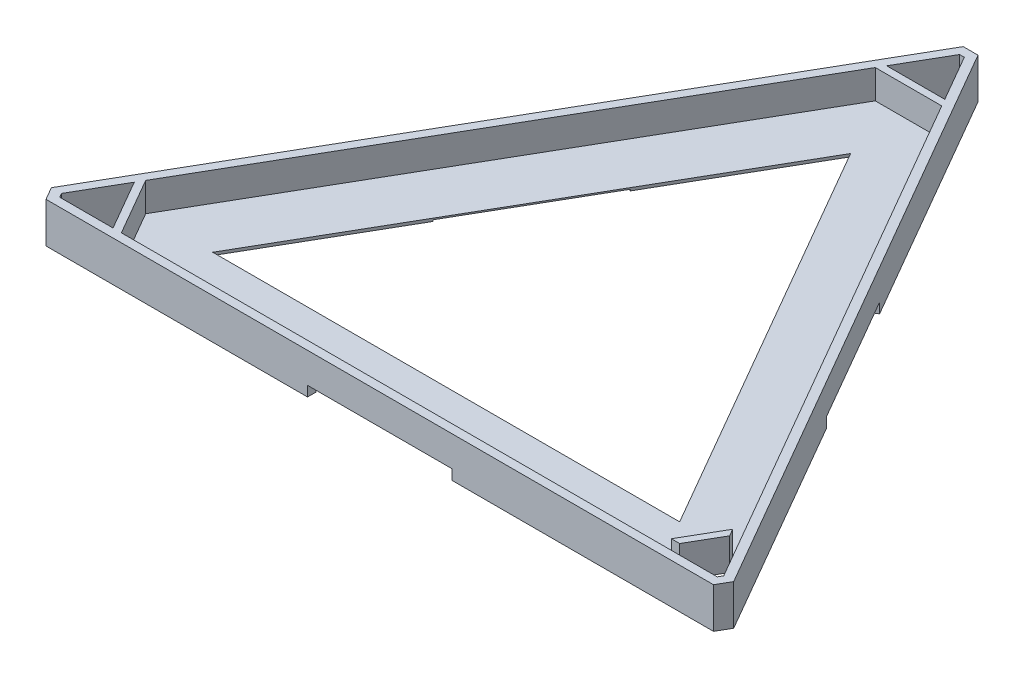
SolidWorks part; units mm, degrees
ref_plane "Front Plane" through (0, 0, 0) normal (0, 0, 1) x (1, 0, 0)
ref_plane "Top Plane" through (0, 0, 0) normal (0, 1, 0) x (1, 0, 0)
ref_plane "Right Plane" through (0, 0, 0) normal (1, 0, 0) x (0, 0, -1)
sketch "Sketch1" plane through (0, 0, 0) normal (0, 1, 0) x (1, 0, 0)
  line L0 (351.2729, 67.6655) -> (468.273, -134.9846)
  line L1 (347.2728, 67.6655) -> (347.2728, 65.1655) construction
  line L2 (409.773, -33.6595) -> (407.6079, -34.9095) construction
  line L3 (468.273, -134.9846) -> (464.2732, -141.9124)
  line L4 (230.2733, -141.9124) -> (464.2732, -141.9124)
  line L5 (230.2733, -141.9124) -> (226.2727, -134.9842)
  line L6 (226.2727, -134.9842) -> (343.2728, 67.6655)
  line L7 (353.4142, 63.9567) -> (351.2491, 62.7067) construction
  line L8 (347.2733, -141.9124) -> (347.2733, -139.4124) construction
  line L9 (231.7167, -139.4124) -> (462.8299, -139.4124)
  line L10 (284.7727, -33.6594) -> (286.9378, -34.9094) construction
  line L11 (344.7161, 65.1655) -> (349.8295, 65.1655)
  line L12 (465.3862, -134.9846) -> (349.8295, 65.1655)
  line L13 (466.2731, -138.4485) -> (464.1081, -137.1985) construction
  line L14 (462.8299, -139.4124) -> (465.3862, -134.9846)
  line L15 (229.1594, -134.9842) -> (344.7161, 65.1655)
  line L16 (229.1594, -134.9842) -> (231.7167, -139.4124)
  line L17 (286.9378, -34.9094) -> (287.3708, -35.1594) construction
  line L18 (230.438, -137.1983) -> (230.871, -136.9483) construction
  line L19 (232.0053, -138.9123) -> (229.7368, -134.9842)
  line L20 (343.2728, 67.6655) -> (351.2729, 67.6655)
  line L21 (345.0048, 64.6655) -> (229.7368, -134.9842)
  line L22 (349.5409, 64.6655) -> (345.0048, 64.6655)
  line L23 (249.0568, -126.4468) -> (246.8918, -127.697) construction
  line L24 (407.6079, -34.9095) -> (407.1749, -35.1595) construction
  line L26 (233.4463, -136.4089) -> (251.9226, -136.4093)
  line L27 (464.8089, -134.9846) -> (462.5412, -138.9123)
  line L28 (462.5412, -138.9123) -> (232.0053, -138.9123)
  line L29 (251.9226, -136.4093) -> (241.8609, -118.9847)
  line L30 (241.8609, -118.9847) -> (232.6236, -134.9842)
  line L31 (232.6236, -134.9842) -> (233.4463, -136.4089)
  line L33 (287.3708, -35.1594) -> (289.5359, -36.4094) construction
  line L34 (254.8093, -136.4089) -> (243.3042, -116.4848)
  line L35 (335.7675, 43.666) -> (243.3042, -116.4848)
  line L36 (358.7782, 43.666) -> (335.7675, 43.666)
  line L38 (289.5359, -36.4094) -> (306.8564, -46.4094) construction
  line L41 (461.939, -134.9846) -> (461.1164, -136.4093)
  line L42 (347.2688, -136.4172) -> (347.2688, -116.4172) construction
  line L43 (442.6021, -136.4093) -> (452.6999, -118.9847)
  line L44 (245.2636, -119.878) -> (249.0568, -126.4468) construction
  line L45 (452.6999, -118.9847) -> (461.939, -134.9846)
  line L48 (461.1164, -136.4093) -> (442.6021, -136.4093)
  line L49 (405.0134, -36.4027) -> (387.6936, -46.404) construction
  line L50 (306.8564, -46.4094) -> (466.2731, -138.4485) construction
  line L51 (357.3348, 46.166) -> (337.2109, 46.166)
  line L52 (337.2109, 46.166) -> (346.4484, 62.1659)
  line L53 (346.4484, 62.1659) -> (348.0966, 62.164)
  line L54 (348.0966, 62.164) -> (357.3348, 46.166)
  line L55 (228.273, -138.4483) -> (387.6936, -46.404) construction
  line L56 (347.2688, -116.4172) -> (347.2728, 43.666) construction
  line L57 (266.4391, -116.428) -> (428.1137, -116.4172)
  line L58 (347.2736, 23.6092) -> (428.1137, -116.4172)
  line L59 (266.4391, -116.428) -> (347.2736, 23.6092)
  line L60 (439.7283, -136.4254) -> (439.7283, -132.9254) construction
  line L61 (451.2487, -116.4715) -> (448.6507, -117.9717) construction
  line L62 (452.6999, -118.9847) -> (358.7782, 43.666)
  line L63 (442.6021, -136.4093) -> (254.8093, -136.4089)
  line L64 (441.749, -132.9254) -> (444.621, -132.9254)
  line L65 (448.6507, -117.9717) -> (450.9647, -121.979) construction
  line L66 (449.5167, -119.4714) -> (450.9647, -121.979)
  line L67 (441.749, -132.9254) -> (449.5167, -119.4714)
  line L68 (450.9647, -121.979) -> (444.621, -132.9254)
  point P13 (407.6079, -34.9095)
  point P20 (464.1081, -137.1985)
  point P23 (347.2733, -139.4124)
  point P25 (347.2732, -141.9124)
  point P27 (347.2728, 65.1655)
  point P31 (286.9378, -34.9094)
  point P37 (287.3708, -35.1594)
  point P39 (230.871, -136.9483)
  point P41 (347.2728, 64.6655)
  point P45 (407.1749, -35.1595)
  point P50 (246.8918, -127.697)
  point P56 (289.5359, -36.4094)
  point P58 (249.0568, -126.4468)
  point P60 (347.2728, 43.666)
  point P62 (345.0048, -136.4089)
  point P64 (445.4885, -126.4485)
  point P71 (447.651, -127.697)
  point P77 (347.2728, 46.166)
  point P84 (347.2688, -116.4172)
  point P87 (387.6936, -46.404)
  point P89 (306.8564, -46.4094)
  point P100 (405.0134, -36.4027)
  dimension "D1" = 2.5
  dimension "D2" = 2.5
  dimension "D3" = 2.5
  dimension "D4" = 2.5
  dimension "D5" = 2.5
  dimension "D6" = 2.5
  dimension "D7" = 0.5
  dimension "D8" = 0.5
  dimension "D9" = 0.5
  dimension "D10" = 2.5
  dimension "D11" = 2.5
  dimension "D12" = 20
  dimension "D13" = 20
  dimension "D14" = 20
  dimension "D15" = 3.5
  dimension "D16" = 3
extrude "Boss-Extrude1" add sketch "Sketch1" along normal blind 1 contours L36 L35 L34 L57 L59 L58 region at (251.4484, 0, 125.0658)
extrude "Boss-Extrude2" add sketch "Sketch1<9>" along normal blind 11 contours L28 L27 L22 L21 L19 L31 L30 L29 L26 L34 L35 L36 L41 L48 L43 L45 L53 L54 L51 L52 | L68 L64 L67 L66 region at (230.7087, 0, 137.042)
sketch "Sketch1<9>" plane through (0, 0, 0) normal (0, 1, 0) x (1, 0, 0) same geometry as "Sketch1"
extrude "Boss-Extrude3" add sketch "Sketch1<10>" along normal blind 5 and the other way blind 3 contours L28 L27 L22 L21 L19 L31 L30 L29 L26 L34 L35 L36 L41 L48 L43 L45 L53 L54 L51 L52 region at (230.7087, 0, 137.042)
sketch "Sketch1<10>" plane through (0, 0, 0) normal (0, 1, 0) x (1, 0, 0) same geometry as "Sketch1"
sketch "Sketch3" plane through (290.5896, 0, -167.772) normal (0.866, 0, -0.5) x (-0.5, 0, -0.866)
  line L1 (-261.593, -6.5) -> (-211.593, -6.5)
  line L2 (-261.593, -6.5) -> (-261.593, 0.5)
  line L3 (-261.593, 0.5) -> (-211.593, 0.5)
  line L4 (-211.593, -6.5) -> (-211.593, 0.5)
  line L5 (-261.593, -6.5) -> (-211.593, 0.5) construction
  line L6 (-261.593, 0.5) -> (-211.593, -6.5) construction
  point P0 (-236.593, -3)
  dimension "D1" = 50
  dimension "D2" = 7
extrude "Cut-Extrude3" cut sketch "Sketch3" against normal blind 25
sketch "Sketch5" plane through (0, 0, 139.4124) normal (0, 0, 1) x (1, 0, 0)
  line L0 (231.7167, -3) -> (462.8299, -3) construction
  line L1 (322.2733, -6.5) -> (372.2733, -6.5)
  line L2 (322.2733, -6.5) -> (322.2733, 0.5)
  line L3 (322.2733, 0.5) -> (372.2733, 0.5)
  line L4 (372.2733, -6.5) -> (372.2733, 0.5)
  line L5 (322.2733, -6.5) -> (372.2733, 0.5) construction
  line L6 (322.2733, 0.5) -> (372.2733, -6.5) construction
  point P0 (347.2733, -3)
  dimension "D1" = 50
  dimension "D2" = 7
extrude "Cut-Extrude4" cut sketch "Sketch5" against normal blind 25
sketch "Sketch6" plane through (230.3194, 0, 132.9752) normal (-0.866, 0, -0.5) x (-0.5, 0, 0.866)
  line L0 (2.3199, -3) -> (-228.7932, -3) construction
  line L1 (-138.2367, -6.5) -> (-88.2367, -6.5)
  line L2 (-138.2367, -6.5) -> (-138.2367, 0.5)
  line L3 (-138.2367, 0.5) -> (-88.2367, 0.5)
  line L4 (-88.2367, -6.5) -> (-88.2367, 0.5)
  line L5 (-138.2367, -6.5) -> (-88.2367, 0.5) construction
  line L6 (-138.2367, 0.5) -> (-88.2367, -6.5) construction
  point P0 (-113.2367, -3)
  dimension "D1" = 50
  dimension "D2" = 7
extrude "Cut-Extrude5" cut sketch "Sketch6" against normal blind 25
